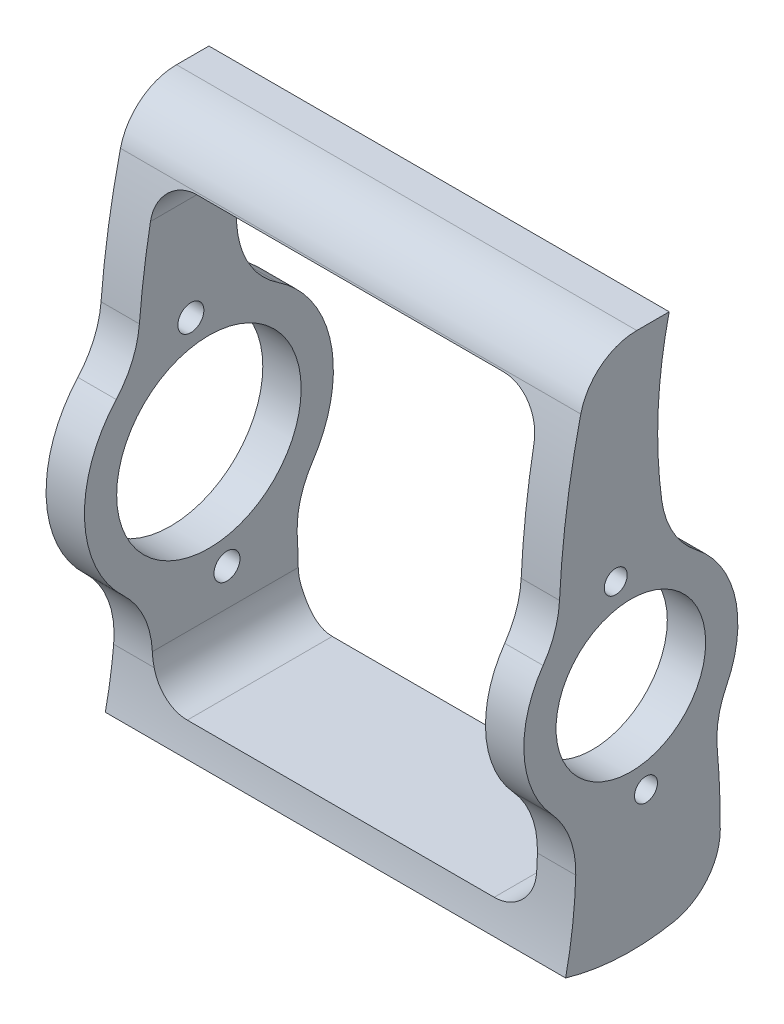
SolidWorks part; units mm, degrees
other "Markup2"
sketch "Sketch9" plane through (31.75, 50.4016, 20.35) normal (0.8402, 0.4575, 0.2911) x (0.3274, 0, -0.9449)
material "AISI 4340 Steel, normalized"
ref_plane "Front Plane" through (0, 0, 0) normal (0, 0, 1) x (1, 0, 0)
ref_plane "Top Plane" through (0, 0, 0) normal (0, 1, 0) x (1, 0, 0)
ref_plane "Right Plane" through (0, 0, 0) normal (1, 0, 0) x (0, 0, -1)
other "Center of Mass"
sketch "Weapon Layout" plane through (0, 0, 0) normal (1, 0, 0) x (0, 0, -1)
  line L0 (-6.35, 50.4016) -> (6.35, 50.4016) construction
  line L1 (-10.8026, -36.5365) -> (14.5626, -35.2071) construction
  line L2 (6.35, 50.4016) -> (-5.4537, 0) construction
  line L3 (6.35, 50.4016) -> (0, 0) construction
  line L4 (0, 0) -> (0, -35.9703) construction
  circle A0 centre (0, 0) radius 14 construction
  circle A1 centre (0, 0) radius 50.8 construction
  circle A2 centre (0, 0) radius 17.175 construction
  circle A3 centre (0, 0) radius 20.35 construction
  arc A4 (-6.35, 50.4016) -> (-20.35, 0) centre (77.3756, 0) ccw construction
  arc A5 (25.0504, -28.707) -> (-25.4024, -28.3959) centre (0, 0) cw construction
  arc A6 (6.35, 50.4016) -> (15.4347, 13.2625) centre (47.4536, 40.7754) ccw construction
  dimension "D1" = 28
  dimension "D2" = 101.6
  dimension "D3" = 3.175
  dimension "D4" = 6.35
  dimension "D5" = 12.7
  dimension "D7" = 6
  dimension "D6" = 12.7
  dimension "D8" = 25.4
  dimension "D9" = 87
sketch "Sketch2" plane through (0, 0, 0) normal (1, 0, 0) x (0, 0, -1)
  line L0 (-6.35, 50.4016) -> (6.35, 50.4016)
  line L1 (-11.3119, -1.6391) -> (0, 0) construction
  line L2 (6.35, 50.4016) -> (-5.4537, 0) construction
  line L3 (-11.6027, 1.0256) -> (-15.24, 50.4016) construction
  arc A0 (-10.8026, -36.5365) -> (14.5626, -35.2071) centre (0, 0) ccw
  arc A1 (-25.4024, -28.3959) -> (25.0504, -28.707) centre (0, 0) ccw construction
  arc A2 (-10.8344, -4.2769) -> (-11.6027, 1.0256) centre (26.3943, 3.8247) cw
  arc A3 (9.8248, 6.4214) -> (11.7322, 0.3423) centre (-25.4469, -7.9841) cw
  arc A4 (-11.6027, 1.0256) -> (-6.35, 50.4016) centre (127.0686, 11.2409) cw
  arc A5 (-10.8344, -4.2769) -> (-10.8026, -36.5365) centre (-85.2917, -20.4799) cw
  arc A6 (6.35, 50.4016) -> (9.8248, 6.4214) centre (76.9988, 33.8561) ccw
  arc A7 (11.7322, 0.3423) -> (14.5626, -35.2071) centre (-112.198, -27.4122) cw
  circle A9 centre (0, 0) radius 11.43 construction
  point P25 (10.9058, 3.4217)
  dimension "D1" = 127
  dimension "D2" = 38.1
  dimension "D3" = 76.2
  dimension "D4" = 38.1
  dimension "D5" = 22.86
  dimension "D6" = 8.89
extrude "Boss-Extrude2" add sketch "Sketch2" along normal mid plane 76.2
sketch "Sketch3" plane through (0, 0, 0) normal (0, 0, 1) x (1, 0, 0)
  line L0 (38.1, 50.4016) -> (-38.1, 50.4016) construction
  line L1 (-31.75, 42.7816) -> (31.75, 42.7816)
  line L2 (-31.75, 42.7816) -> (-31.75, -31.75)
  line L3 (-31.75, -31.75) -> (31.75, -31.75)
  line L4 (31.75, 42.7816) -> (31.75, -31.75)
  line L6 (-38.1, -38.1) -> (38.1, -38.1) construction
  line L7 (-38.1, 50.4016) -> (-38.1, 1.0256) construction
  dimension "D4" = 6.35
  dimension "D1" = 7.62
  dimension "D3" = 6.35
  dimension "D2" = 6.35
extrude "Cut-Extrude1" cut sketch "Sketch3" against normal through all both and the other way through all
fillet "Fillet1" radius 6.35 4 edges at (-31.75, 42.7816, 1.6822) (31.75, 42.7816, 1.6822) (31.75, -31.75, -2.3991) (-31.75, -31.75, -2.3991)
fillet "Fillet3" radius 9.525 2 edges at (0, -35.2071, -14.5626) (0, 50.4016, 6.35)
sketch "Sketch6" plane through (-38.1, 0, 0) normal (-1, 0, 0) x (0, 0, 1)
  circle A0 centre (0, 0) radius 20.604
  dimension "D1" = 41.208
extrude "Boss-Extrude3" add sketch "Sketch6" against normal up to surface (6.35 mm away) up to face at (-31.75, 3.1892, 0.2294)
sketch "Sketch7" plane through (-38.1, 0, 0) normal (-1, 0, 0) x (0, 0, 1)
  circle A0 centre (0, 0) radius 15.27
  arc A1 (9.1181, -18.4766) -> (11.8655, 16.8444) centre (0, 0) ccw construction
  dimension "D1" = 30.54
extrude "Cut-Extrude3" cut sketch "Sketch7" against normal up to next
sketch "Sketch10" plane through (38.1, 0, 0) normal (1, 0, 0) x (0, 0, -1)
  circle A0 centre (0, 0) radius 17.7165
  dimension "D1" = 35.433
extrude "Boss-Extrude4" add sketch "Sketch10" against normal up to surface (6.35 mm away) up to face at (31.75, 3.1892, 0.2294)
sketch "Sketch5" plane through (38.1, 0, 0) normal (1, 0, 0) x (0, 0, -1)
  circle A0 centre (0, 0) radius 12.3825
  circle A1 centre (0, 0) radius 6.35 construction
  dimension "D1" = 12.7
  dimension "D2" = 24.765
extrude "Cut-Extrude2" cut sketch "Sketch5" against normal up to next
fillet "Fillet2" radius 15.24 8 edges at (-34.925, 16.8444, 11.8655) (-34.925, -18.4766, 9.1181) (-34.925, -14.9406, -14.1881) (-34.925, 19.765, -5.8198) (34.925, 16.4593, -6.5548) (34.925, -11.162, -13.7581) (34.925, -15.09, 9.2826) (34.925, 13.0644, 11.9665)
sketch "Sketch11" plane through (38.1, 0, 0) normal (1, 0, 0) x (0, 0, -1)
  circle A0 centre (-2.502, 16.1587) radius 1.8986
  circle A1 centre (-2.502, 16.1587) radius 1.8986 construction
  circle A2 centre (2.502, -16.1587) radius 1.8987
  circle A3 centre (2.502, -16.1587) radius 1.8986 construction
extrude "Cut-Extrude4" cut sketch "Sketch11" against normal up to surface (6.35 mm away) up to face at (31.75, 12.3825, 0)
hole_wizard "#6 Clearance Hole1" positions "Sketch12" profile "Sketch13" hole size "#6" standard "ANSI Inch"
sketch "Sketch12" plane through (-38.1, 0, 0) normal (1, 0, 0) x (0, 0, -1)
  point P0 (-2.9885, 19.3009)
  point P3 (2.9885, -19.3009)
sketch "Sketch13" plane through (-38.1, 19.3009, 2.9885) normal (0, 1, 0) x (0, 0, 1)
  line L0 (0, 0) -> (0, 8.9134)
  line L1 (0, 8.9134) -> (2.1526, 7.62)
  line L2 (2.1526, 7.62) -> (2.1526, 0)
  line L5 (2.1526, 0) -> (0, 0)
  line L10 (0, 8.9134) -> (-2.1527, 7.62) construction
  line L11 (0, -6.35) -> (0, 107.95) construction
  dimension "Hole Dia." = 4.3053
  dimension "Hole Depth" = 7.62
  dimension "Drill Angle" = 118
other "Center of Mass Reference Point1"
equation "\"D1@Weapon Layout\" = 28mm"
equation "\"D1@Sketch6\"=\"bearing OD L\"+.42in+0.1in"
equation "\"D2@Sketch3\"=\"D3@Sketch3\""
equation "\"D1@Sketch7\"=\"bearing OD L\"+0.1in"
equation "\"D2@Sketch5\"=\"bearing OD R\" + .1"
equation "\"D1@Sketch10\"=\"bearing OD R\" + 0.42 + .1"
equation "\"bearing OD R\"= 7 / 8"
equation "\"bearing OD L\"= 28mm"
